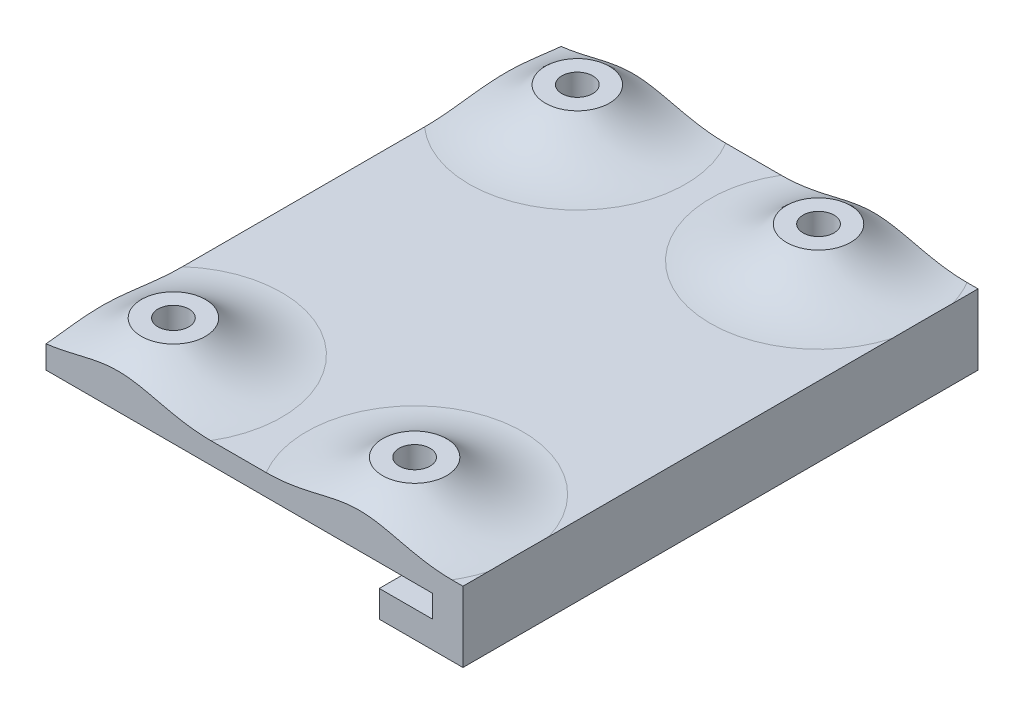
SolidWorks part; units mm, degrees
ref_plane "Front Plane" through (0, 0, 0) normal (0, 0, 1) x (1, 0, 0)
ref_plane "Top Plane" through (0, 0, 0) normal (0, 1, 0) x (1, 0, 0)
ref_plane "Right Plane" through (0, 0, 0) normal (1, 0, 0) x (0, 0, -1)
sketch "Esquisse1" plane through (0, 0, 0) normal (0, 1, 0) x (1, 0, 0)
  line L1 (-18.034, 24.13) -> (18.034, 24.13)
  line L2 (-18.034, 24.13) -> (-18.034, -24.13)
  line L3 (-18.034, -24.13) -> (18.034, -24.13)
  line L4 (18.034, 24.13) -> (18.034, -24.13)
  line L5 (-18.034, 24.13) -> (18.034, -24.13) construction
  line L6 (-18.034, -24.13) -> (18.034, 24.13) construction
  point P0 (0, 0)
extrude "Boss.-Extru.1" add sketch "Esquisse1" along normal blind 2
ref_plane "Plan1" through (0, 0, 0) normal (1, 0, 0) x (0, 0, -1)
sketch "Esquisse4" plane through (0, 2, 0) normal (0, 1, 0) x (1, 0, 0)
  line L0 (0, -8.2401) -> (0, 8.2401) construction
  line L1 (18.034, -24.13) -> (18.034, 24.13) construction
  circle A0 centre (11.3, 18.921) radius 3
  circle A1 centre (11.3, -18.925) radius 3
  point P7 (18.034, 0)
  dimension "D1" = 37.846
  dimension "D3" = 11.3
  dimension "D4" = 11.3
  dimension "D2" = 18.925
extrude "Boss.-Extru.2" add sketch "Esquisse4" along normal blind 3
sketch "Esquisse6" plane through (0, 5, 0) normal (0, 1, 0) x (1, 0, 0)
  circle A0 centre (11.3, 18.921) radius 1.45
  circle A1 centre (11.3, -18.925) radius 1.45
extrude "Enlèv. mat.-Extru.1" cut sketch "Esquisse6" against normal through all
mirror "Symétrie1" about plane through (0, 0, 0) normal (1, 0, 0) of "Boss.-Extru.2", "Enlèv. mat.-Extru.1"
sketch "Esquisse10" plane through (18.034, 0, 0) normal (1, 0, 0) x (0, 0, -1)
  line L1 (24.13, 2) -> (-24.13, 2)
  line L2 (24.13, 2) -> (24.13, 0)
  line L3 (24.13, 0) -> (-24.13, 0)
  line L4 (-24.13, 2) -> (-24.13, 0)
extrude "Boss.-Extru.3" add sketch "Esquisse10" along normal blind 3
sketch "Esquisse11" plane through (0, 0, 0) normal (0, -1, 0) x (-1, 0, 0)
  line L0 (18.034, -24.13) -> (-21.034, -24.13) construction
  line L1 (-21.034, 24.13) -> (-18.1944, 24.13)
  line L2 (-21.034, 24.13) -> (-21.034, -24.13)
  line L3 (-21.034, -24.13) -> (-18.1944, -24.13)
  line L4 (-18.1944, 24.13) -> (-18.1944, -24.13)
extrude "Boss.-Extru.4" add sketch "Esquisse11" along normal blind 4.6
sketch "Esquisse12" plane through (18.1944, 0, 0) normal (-1, 0, 0) x (0, 0, 1)
  line L0 (-24.13, -4.6) -> (-24.13, 0) construction
  line L1 (24.13, -4.6) -> (-24.13, -4.6)
  line L2 (24.13, -4.6) -> (24.13, -2.1)
  line L3 (24.13, -2.1) -> (-24.13, -2.1)
  line L4 (-24.13, -4.6) -> (-24.13, -2.1)
  line L5 (-24.13, 0) -> (24.13, 0) construction
  dimension "D1" = 2.1
extrude "Boss.-Extru.5" add sketch "Esquisse12" along normal blind 5
fillet "Congé1" radius 10 2 edges at (-11.3, 2, -15.921) (-11.3, 2, 21.925)
fillet "Congé2" radius 10 2 edges at (11.3, 2, 21.925) (11.3, 2, -15.921)
